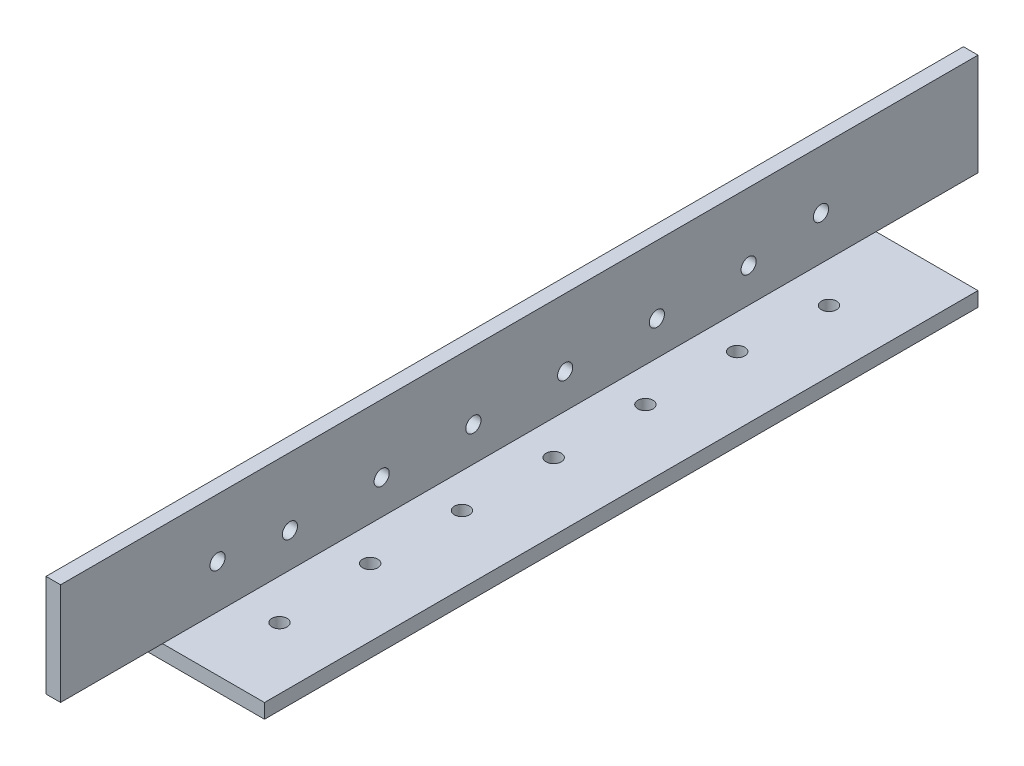
SolidWorks part; units mm, degrees
ref_plane "Front Plane" through (0, 0, 0) normal (0, 0, 1) x (1, 0, 0)
ref_plane "Top Plane" through (0, 0, 0) normal (0, 1, 0) x (1, 0, 0)
ref_plane "Right Plane" through (0, 0, 0) normal (1, 0, 0) x (0, 0, -1)
sketch "Sketch1" plane through (0, 0, 0) normal (0, 0, 1) x (1, 0, 0)
  line L0 (0, 25.4) -> (0, 0) construction
  line L1 (0, 0) -> (25.4, 0) construction
  line L2 (25.4, 0) -> (25.4, 3.175) construction
  line L3 (25.4, 3.175) -> (3.175, 3.175) construction
  line L4 (3.175, 3.175) -> (3.175, 25.4) construction
  line L6 (3.175, 25.4) -> (0, 25.4) construction
  arc A0 (3.175, 3.5814) -> (3.5814, 3.175) centre (3.5814, 3.5814) ccw construction
  point P4 (0, 0)
  dimension "Inside Corner Radius" = 0.4064
  dimension "Outside Height" = 25.4
  dimension "Inside Height" = 22.225
  dimension "Outside Width" = 25.4
  dimension "Inside Width" = 22.225
  dimension "Wall Thickness" = 3.175
  dimension "Shape" = 90
sketch "Sketch2" plane through (0, 0, 0) normal (1, 0, 0) x (0, 0, -1)
  line L0 (1219.2, 0) -> (-1219.2, 0) construction
  line L1 (-1219.2, 25.4) -> (-1219.2, 0) construction
  line L2 (1219.2, 25.4) -> (1219.2, 0) construction
  point P0 (-1189.99, 0)
  point P4 (0, 0)
  point P6 (1189.99, 0)
  dimension "D1" = 29.21
  dimension "D2" = 29.21
  dimension "D3" = 25.4
  dimension "Length" = 2438.4
sketch "Sketch3" plane through (0, 0, 0) normal (0, 0, 1) x (1, 0, 0)
  line L0 (3.175, 25.4) -> (0, 25.4)
  line L1 (0, 25.4) -> (0, 0)
  line L2 (0, 0) -> (25.4, 0)
  line L3 (25.4, 0) -> (25.4, 3.175)
  line L4 (25.4, 3.175) -> (3.175, 3.175)
  line L5 (3.175, 3.175) -> (3.175, 25.4)
extrude "Boss-Extrude1" add sketch "Sketch3" along normal mid plane 2438.4
fillet "Fillet1" radius 0.4064 1 edges at (3.175, 3.175, 0)
sketch "Sketch4" plane through (0, 0, 0) normal (-1, 0, 0) x (0, 0, 1)
  line L0 (1219.2, 25.4) -> (1219.2, 0) construction
  line L1 (-1219.2, 25.4) -> (1019.2, 25.4)
  line L2 (-1219.2, 25.4) -> (-1219.2, -77.8785)
  line L3 (-1219.2, -77.8785) -> (1019.2, -77.8785)
  line L4 (1019.2, 25.4) -> (1019.2, -77.8785)
  dimension "D1" = 200
extrude "Cut-Extrude1" cut sketch "Sketch4" against normal blind 60
sketch "Sketch5" plane through (0, 0, 0) normal (0, -1, 0) x (1, 0, 0)
  line L0 (0, 1219.2) -> (0, 1019.2) construction
  line L1 (25.4, 1019.2) -> (0, 1019.2)
  line L2 (25.4, 1019.2) -> (25.4, 1041.43)
  line L3 (25.4, 1041.43) -> (0, 1041.43)
  line L4 (0, 1019.2) -> (0, 1041.43)
  dimension "D1" = 22.23
extrude "Cut-Extrude2" cut sketch "Sketch5" against normal up to surface (3.175 mm away) up to face at (14.4907, 3.175, 1119.2)
sketch "Sketch6" plane through (0, 0, 0) normal (0, -1, 0) x (1, 0, 0)
  line L0 (0, 1219.2) -> (0, 1041.43) construction
  line L1 (25.4, 1219.2) -> (0, 1219.2)
  line L2 (25.4, 1219.2) -> (25.4, 1196.97)
  line L3 (25.4, 1196.97) -> (0, 1196.97)
  line L4 (0, 1219.2) -> (0, 1196.97)
  dimension "D1" = 22.23
extrude "Cut-Extrude3" cut sketch "Sketch6" against normal up to surface (3.175 mm away) up to face at (14.4907, 3.175, 1130.315)
sketch "Sketch7" plane through (0, 0, 1019.2) normal (0, 0, -1) x (-1, 0, 0)
  line L0 (-3.175, 3.5814) -> (-3.175, 25.4) construction
  line L1 (-3.175, 4.2) -> (-4.4439, 4.2)
  line L2 (-3.175, 4.2) -> (-3.175, 3.175)
  line L3 (-3.175, 3.175) -> (-4.4439, 3.175)
  line L4 (-4.4439, 4.2) -> (-4.4439, 3.175)
  line L5 (-3.5814, 3.175) -> (-25.4, 3.175) construction
extrude "Cut-Extrude4" cut sketch "Sketch7" against normal blind 220
sketch "Sketch9" plane through (3.175, 0, 0) normal (1, 0, 0) x (0, 0, -1)
  line L0 (-1219.2, 3.175) -> (-1219.2, 25.4) construction
  line L1 (-1196.97, 3.175) -> (-1041.43, 3.175) construction
  line L2 (-1019.2, 3.175) -> (-1019.2, 25.4) construction
  circle A0 centre (-1169.2, 10.675) radius 1.65
  circle A1 centre (-1149.2, 10.675) radius 1.65
  circle A2 centre (-1129.2, 10.675) radius 1.65
  circle A3 centre (-1109.2, 10.675) radius 1.65
  circle A4 centre (-1089.2, 10.675) radius 1.65
  circle A5 centre (-1069.2, 10.675) radius 1.65
  dimension "D1" = 50
  dimension "D2" = 7.5
  dimension "D3" = 3.3
  dimension "D5" = 50
  dimension "D4" = 6
extrude "Cut-Extrude5" cut sketch "Sketch9" against normal blind 20
sketch "Sketch10" plane through (0, 3.175, 0) normal (0, 1, 0) x (1, 0, 0)
  line L0 (600, -1019.2) -> (0, -1019.2) construction
  line L1 (3.175, -1196.97) -> (3.175, -1041.43) construction
  circle A0 centre (10.675, -1079.2) radius 1.65
  circle A1 centre (10.675, -1099.2) radius 1.65
  circle A2 centre (10.675, -1119.2) radius 1.65
  circle A3 centre (10.675, -1139.2) radius 1.65
  circle A4 centre (10.675, -1159.2) radius 1.65
  dimension "D1" = 60
  dimension "D2" = 7.5
  dimension "D3" = 3.3
  dimension "D5" = 20
  dimension "D4" = 5
extrude "Cut-Extrude6" cut sketch "Sketch10" against normal blind 20
sketch "Sketch11" plane through (3.175, 0, 0) normal (1, 0, 0) x (0, 0, -1)
  circle A0 centre (-1053.4257, 12.7) radius 1.65
  circle A1 centre (-1184.9793, 12.7) radius 1.65
  dimension "D1" = 3.3
extrude "Cut-Extrude7" cut sketch "Sketch11" against normal blind 70
sketch "Sketch12" plane through (0, 3.175, 0) normal (0, 1, 0) x (1, 0, 0)
  circle A0 centre (11.9634, -1180.2606) radius 1.65
  circle A1 centre (11.9634, -1060.48) radius 1.65
  dimension "D1" = 3.3
extrude "Cut-Extrude8" cut sketch "Sketch12" against normal blind 70
equation "\"D1@Boss-Extrude1\"=\"Length@Sketch2\""
equation "\"D1@Sketch2\" = \"Outside Width@Sketch1\" * 1.15"
equation "\"D2@Sketch2\"=\"D1@Sketch2\""
equation "\"D1@Fillet1\"=\"Inside Corner Radius@Sketch1\""
equation "\"D3@Sketch2\"=\"Outside Height@Sketch1\""
